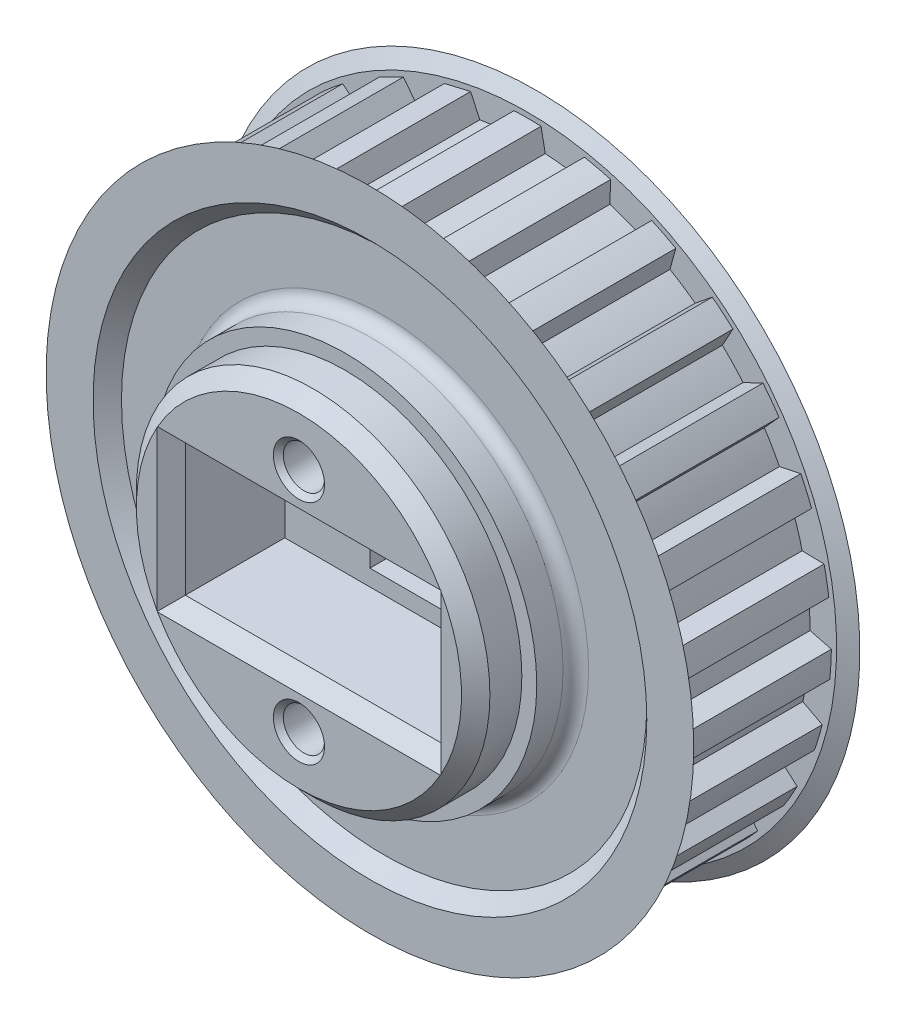
SolidWorks part; units mm, degrees
other "Markup1"
sketch "Sketch8" plane through (-22.8072, 22.8072, -5) normal (-0.0228, 0.8013, -0.5978) x (-0.0343, -0.5983, -0.8006)
material "ABS"
ref_plane "Alzado" through (0, 0, 0) normal (0, 0, 1) x (1, 0, 0)
ref_plane "Planta" through (0, 0, 0) normal (0, 1, 0) x (1, 0, 0)
ref_plane "Vista lateral" through (0, 0, 0) normal (1, 0, 0) x (0, 0, -1)
sketch "Croquis1" plane through (0, 0, 0) normal (0, 0, 1) x (1, 0, 0)
  line L0 (0, 0) -> (0, 14.5885) construction
  line L1 (-0.95, 21.3789) -> (-1.25, 19.8607)
  line L2 (0.95, 21.3789) -> (1.25, 19.8607)
  line L3 (5.8547, 20.5835) -> (5.7965, 19.0371)
  line L4 (4.0059, 21.0217) -> (3.3639, 19.6136)
  line L5 (10.4438, 18.6785) -> (10.0305, 17.1872)
  line L6 (8.7459, 19.5312) -> (7.7964, 18.3092)
  line L7 (14.4698, 15.7665) -> (13.7238, 14.4107)
  line L8 (13.0144, 16.9878) -> (11.8087, 16.0177)
  line L9 (17.7158, 12.0046) -> (16.6772, 10.8573)
  line L10 (16.5812, 13.5286) -> (15.1843, 12.8626)
  line L11 (20.0067, 7.5954) -> (18.7315, 6.7187)
  line L12 (19.2542, 9.3401) -> (17.7413, 9.0142)
  line L13 (21.2191, 2.7768) -> (19.776, 2.2178)
  line L14 (20.8891, 4.648) -> (19.3419, 4.6798)
  line L15 (21.2875, -2.1915) -> (19.7544, -2.4027)
  line L16 (21.398, -0.2947) -> (19.8998, 0.0931)
  line L17 (20.2083, -7.0416) -> (18.6678, -6.8936)
  line L18 (20.7532, -5.2214) -> (19.3848, -4.4986)
  line L19 (18.0397, -11.5122) -> (16.5749, -11.0129)
  line L20 (18.9897, -9.8667) -> (17.8249, -8.8478)
  line L21 (14.8985, -15.3621) -> (13.5883, -14.5385)
  line L22 (16.2024, -13.9801) -> (15.304, -12.72)
  line L23 (10.9542, -18.3838) -> (9.8693, -17.2803)
  line L24 (12.5416, -17.3398) -> (11.958, -15.9065)
  line L25 (6.4193, -20.4145) -> (5.6181, -19.0905)
  line L26 (8.2047, -19.7647) -> (7.9674, -18.2354)
  line L27 (1.5384, -21.3446) -> (1.0641, -19.8715)
  line L28 (3.4255, -21.1241) -> (3.5472, -19.5813)
  line L29 (-3.4255, -21.1241) -> (-3.5472, -19.5813)
  line L30 (-1.5384, -21.3446) -> (-1.0641, -19.8715)
  line L31 (-8.2047, -19.7647) -> (-7.9674, -18.2354)
  line L32 (-6.4193, -20.4145) -> (-5.6181, -19.0905)
  line L33 (-12.5416, -17.3398) -> (-11.958, -15.9065)
  line L34 (-10.9542, -18.3838) -> (-9.8693, -17.2803)
  line L35 (-16.2024, -13.9801) -> (-15.304, -12.72)
  line L36 (-14.8985, -15.3621) -> (-13.5883, -14.5385)
  line L37 (-18.9897, -9.8667) -> (-17.8249, -8.8478)
  line L38 (-18.0397, -11.5122) -> (-16.5749, -11.0129)
  line L39 (-20.7532, -5.2214) -> (-19.3848, -4.4986)
  line L40 (-20.2083, -7.0416) -> (-18.6678, -6.8936)
  line L41 (-21.398, -0.2947) -> (-19.8998, 0.0931)
  line L42 (-21.2875, -2.1915) -> (-19.7544, -2.4027)
  line L43 (-20.8891, 4.648) -> (-19.3419, 4.6798)
  line L44 (-21.2191, 2.7768) -> (-19.776, 2.2178)
  line L45 (-19.2542, 9.3401) -> (-17.7413, 9.0142)
  line L46 (-20.0067, 7.5954) -> (-18.7315, 6.7187)
  line L47 (-16.5812, 13.5286) -> (-15.1843, 12.8626)
  line L48 (-17.7158, 12.0046) -> (-16.6772, 10.8573)
  line L49 (-13.0144, 16.9878) -> (-11.8087, 16.0177)
  line L50 (-14.4698, 15.7665) -> (-13.7238, 14.4107)
  line L51 (-8.7459, 19.5312) -> (-7.7964, 18.3092)
  line L52 (-10.4438, 18.6785) -> (-10.0305, 17.1872)
  line L53 (-10.4438, 18.6785) -> (-8.7459, 19.5312)
  line L54 (-4.0059, 21.0217) -> (-3.3639, 19.6136)
  line L55 (-5.8547, 20.5835) -> (-5.7965, 19.0371)
  line L56 (-5.8547, 20.5835) -> (-4.0059, 21.0217)
  arc A0 (-10.0305, 17.1872) -> (-11.8087, 16.0177) centre (0, 0) ccw
  arc A1 (3.3639, 19.6136) -> (1.25, 19.8607) centre (0, 0) ccw
  arc A2 (-5.7965, 19.0371) -> (-7.7964, 18.3092) centre (0, 0) ccw
  arc A9 (-13.0144, 16.9878) -> (-14.4698, 15.7665) centre (0, 0) ccw
  arc A10 (-16.5812, 13.5286) -> (-17.7158, 12.0046) centre (0, 0) ccw
  arc A11 (5.8547, 20.5835) -> (4.0059, 21.0217) centre (0, 0) ccw
  arc A12 (0.95, 21.3789) -> (-0.95, 21.3789) centre (0, 0) ccw
  arc A16 (10.4438, 18.6785) -> (8.7459, 19.5312) centre (0, 0) ccw
  arc A17 (14.4698, 15.7665) -> (13.0144, 16.9878) centre (0, 0) ccw
  arc A18 (17.7158, 12.0046) -> (16.5812, 13.5286) centre (0, 0) ccw
  arc A19 (20.0067, 7.5954) -> (19.2542, 9.3401) centre (0, 0) ccw
  arc A20 (21.2191, 2.7768) -> (20.8891, 4.648) centre (0, 0) ccw
  arc A21 (21.2875, -2.1915) -> (21.398, -0.2947) centre (0, 0) ccw
  arc A22 (20.2083, -7.0416) -> (20.7532, -5.2214) centre (0, 0) ccw
  arc A23 (18.0397, -11.5122) -> (18.9897, -9.8667) centre (0, 0) ccw
  arc A24 (14.8985, -15.3621) -> (16.2024, -13.9801) centre (0, 0) ccw
  arc A25 (10.9542, -18.3838) -> (12.5416, -17.3398) centre (0, 0) ccw
  arc A26 (-8.2047, -19.7647) -> (-6.4193, -20.4145) centre (0, 0) ccw
  arc A27 (-12.5416, -17.3398) -> (-10.9542, -18.3838) centre (0, 0) ccw
  arc A28 (-16.2024, -13.9801) -> (-14.8985, -15.3621) centre (0, 0) ccw
  arc A29 (-20.7532, -5.2214) -> (-20.2083, -7.0416) centre (0, 0) ccw
  arc A30 (-21.398, -0.2947) -> (-21.2875, -2.1915) centre (0, 0) ccw
  arc A31 (-20.8891, 4.648) -> (-21.2191, 2.7768) centre (0, 0) ccw
  arc A32 (-19.2542, 9.3401) -> (-20.0067, 7.5954) centre (0, 0) ccw
  arc A33 (-3.4255, -21.1241) -> (-1.5384, -21.3446) centre (0, 0) ccw
  arc A34 (1.5384, -21.3446) -> (3.4255, -21.1241) centre (0, 0) ccw
  arc A35 (6.4193, -20.4145) -> (8.2047, -19.7647) centre (0, 0) ccw
  arc A36 (7.7964, 18.3092) -> (5.7965, 19.0371) centre (0, 0) ccw
  arc A37 (11.8087, 16.0177) -> (10.0305, 17.1872) centre (0, 0) ccw
  arc A39 (-1.25, 19.8607) -> (-3.3639, 19.6136) centre (0, 0) ccw
  arc A43 (15.1843, 12.8626) -> (13.7238, 14.4107) centre (0, 0) ccw
  arc A44 (17.7413, 9.0142) -> (16.6772, 10.8573) centre (0, 0) ccw
  arc A45 (19.3419, 4.6798) -> (18.7315, 6.7187) centre (0, 0) ccw
  arc A46 (19.8998, 0.0931) -> (19.776, 2.2178) centre (0, 0) ccw
  arc A47 (19.3848, -4.4986) -> (19.7544, -2.4027) centre (0, 0) ccw
  arc A48 (17.8249, -8.8478) -> (18.6678, -6.8936) centre (0, 0) ccw
  arc A49 (15.304, -12.72) -> (16.5749, -11.0129) centre (0, 0) ccw
  arc A50 (11.958, -15.9065) -> (13.5883, -14.5385) centre (0, 0) ccw
  arc A51 (7.9674, -18.2354) -> (9.8693, -17.2803) centre (0, 0) ccw
  arc A52 (3.5472, -19.5813) -> (5.6181, -19.0905) centre (0, 0) ccw
  arc A53 (-1.0641, -19.8715) -> (1.0641, -19.8715) centre (0, 0) ccw
  arc A54 (-5.6181, -19.0905) -> (-3.5472, -19.5813) centre (0, 0) ccw
  arc A55 (-9.8693, -17.2803) -> (-7.9674, -18.2354) centre (0, 0) ccw
  arc A56 (-13.5883, -14.5385) -> (-11.958, -15.9065) centre (0, 0) ccw
  arc A57 (-16.5749, -11.0129) -> (-15.304, -12.72) centre (0, 0) ccw
  arc A58 (-18.6678, -6.8936) -> (-17.8249, -8.8478) centre (0, 0) ccw
  arc A59 (-19.7544, -2.4027) -> (-19.3848, -4.4986) centre (0, 0) ccw
  arc A60 (-19.776, 2.2178) -> (-19.8998, 0.0931) centre (0, 0) ccw
  arc A61 (-18.7315, 6.7187) -> (-19.3419, 4.6798) centre (0, 0) ccw
  arc A62 (-16.6772, 10.8573) -> (-17.7413, 9.0142) centre (0, 0) ccw
  arc A63 (-13.7238, 14.4107) -> (-15.1843, 12.8626) centre (0, 0) ccw
  arc A71 (-18.9897, -9.8667) -> (-18.0397, -11.5122) centre (0, 0) ccw
  circle A72 centre (0, 0) radius 1.5
  point P151 (0, 0)
  dimension "D1" = 21.4
  dimension "D6" = 3
  dimension "D5" = 1.5
  dimension "D2" = 2.5
  dimension "D3" = 1.9
  dimension "D4" = 27
extrude "Saliente-Extruir1" add sketch "Croquis1" along normal blind 10.5
sketch "Croquis2" plane through (0, 0, 10.5) normal (0, 0, 1) x (1, 0, 0)
  circle A0 centre (0, 0) radius 23.5
  circle A1 centre (0, 0) radius 1.5
  circle A2 centre (0, 0) radius 1.5 construction
  dimension "D1" = 47
extrude "Saliente-Extruir2" add sketch "Croquis2" along normal blind 0.6
sketch "Croquis3" plane through (0, 0, 11.1) normal (0, 0, 1) x (1, 0, 0)
  circle A0 centre (0, 0) radius 1.5
  circle A1 centre (0, 0) radius 12.45
  circle A3 centre (0, 0) radius 1.5 construction
  dimension "D1" = 24.9
sketch "Croquis4" plane through (0, 0, 0) normal (0, 0, -1) x (-1, 0, 0)
  circle A0 centre (0, 0) radius 1.5
  circle A1 centre (0, 0) radius 12.45
  circle A2 centre (0, 0) radius 1.5 construction
  dimension "D1" = 24.9
extrude "Saliente-Extruir4" add sketch "Croquis4" along normal blind 5.25
sketch "Croquis6" plane through (0, 0, 0) normal (0, 0, -1) x (-1, 0, 0)
  circle A0 centre (0, 0) radius 23.5
  circle A1 centre (0, 0) radius 1.5
  circle A2 centre (0, 0) radius 1.5 construction
  dimension "D1" = 47
extrude "Saliente-Extruir6" add sketch "Croquis6" along normal blind 0.6
sketch "Sketch6" plane through (0, 0, -0.6) normal (0, 0, -1) x (-1, 0, 0)
  circle A0 centre (0, 0) radius 12.45
  circle A1 centre (0, 0) radius 18.5
  circle A2 centre (0, 0) radius 12.45 construction
  dimension "D1" = 37
extrude "Cut-Extrude3" cut sketch "Sketch6" against normal blind 1
sketch "Croquis5" plane through (0, 0, 0.4) normal (0, 0, -1) x (-1, 0, 0)
  circle A0 centre (0, 0) radius 1.5
  circle A1 centre (0, 0) radius 13.5
  circle A2 centre (0, 0) radius 1.5 construction
  dimension "D1" = 27
extrude "Saliente-Extruir5" add sketch "Croquis5" along normal blind 2.65
chamfer "Chaflán2" distance 1 angle 60 2 edges at (-23.5, 0, 0) (23.5, 0, 10.5)
extrude "Saliente-Extruir7" add sketch "Croquis3" along normal blind 5
sketch "Sketch7" plane through (0, 0, 11.1) normal (0, 0, 1) x (1, 0, 0)
  circle A0 centre (0, 0) radius 12.45
  circle A1 centre (0, 0) radius 18.5
  circle A2 centre (0, 0) radius 12.45 construction
  dimension "D1" = 37
extrude "Cut-Extrude4" cut sketch "Sketch7" against normal blind 1
chamfer "Chaflán4" distance 1 angle 45 1 edges at (12.45, 0, 16.1)
sketch "Croquis7" plane through (0, 0, 10.1) normal (0, 0, 1) x (1, 0, 0)
  circle A0 centre (0, 0) radius 1.5
  circle A1 centre (0, 0) radius 13.5
  circle A2 centre (0, 0) radius 1.5 construction
  dimension "D1" = 27
extrude "Saliente-Extruir8" add sketch "Croquis7" along normal blind 2.75
sketch "Croquis8" plane through (0, 0, 0) normal (0, 0, 1) x (1, 0, 0)
  line L0 (0, 0) -> (6.706, 0) construction
  line L1 (-3, 3.5) -> (3, 3.5)
  line L2 (-3, 3.5) -> (-3, -3.5)
  line L3 (-3, -3.5) -> (3, -3.5)
  line L4 (3, 3.5) -> (3, -3.5)
  line L5 (-3, 3.5) -> (3, -3.5) construction
  line L6 (-3, -3.5) -> (3, 3.5) construction
  circle A0 centre (0, 8) radius 1.45
  circle A1 centre (0, -8) radius 1.45
  point P0 (0, 0)
  dimension "D1" = 2.9
  dimension "D2" = 7
  dimension "D3" = 6
  dimension "D4" = 16
extrude "Cortar-Extruir1" cut sketch "Croquis8" against normal through all both and the other way through all
sketch "Croquis10" plane through (0, 0, 16.1) normal (0, 0, 1) x (1, 0, 0)
  line L1 (9, 4.65) -> (-9, 4.65)
  line L2 (9, 4.65) -> (9, -4.65)
  line L3 (9, -4.65) -> (-9, -4.65)
  line L4 (-9, 4.65) -> (-9, -4.65)
  line L5 (9, 4.65) -> (-9, -4.65) construction
  line L6 (9, -4.65) -> (-9, 4.65) construction
  point P0 (0, 0)
  dimension "D1" = 9.3
  dimension "D2" = 18
extrude "Cortar-Extruir3" cut sketch "Croquis10" against normal blind 8
chamfer "Chaflán5" distance 1 angle 45 8 edges at (-3, 0, -5.25) (0, 3.5, -5.25) (3, 0, -5.25) (0, -3.5, -5.25) (9, 0, 16.1) (0, 4.65, 16.1) (-9, 0, 16.1) (0, -4.65, 16.1)
sketch "Sketch1" plane through (0, 0, -5.25) normal (0, 0, -1) x (-1, 0, 0)
  circle A0 centre (0, 0) radius 12.45
  circle A1 centre (0, 0) radius 12.45 construction
  circle A2 centre (0, 8) radius 1.45
  circle A3 centre (0, -8) radius 1.45
  circle A4 centre (0, 8) radius 1.45 construction
extrude "Boss-Extrude1" add sketch "Sketch1" against normal blind 5
sketch "Sketch2" plane through (0, 0, -5.25) normal (0, 0, -1) x (-1, 0, 0)
  line L0 (0, 17.274) -> (0, -20.0751) construction
  line L1 (-6.5, 0) -> (6.5, 0) construction
  circle A0 centre (-6.5, 0) radius 1.45
  circle A1 centre (6.5, 0) radius 1.45
  dimension "D1" = 2.9
  dimension "D2" = 13
extrude "Cut-Extrude1" cut sketch "Sketch2" against normal through all
sketch "Sketch4" plane through (0, 0, 16.1) normal (0, 0, 1) x (1, 0, 0)
  line L0 (-3, -3.5) -> (3, -3.5) construction
  line L1 (3, 3.5) -> (-3, 3.5)
  line L2 (3, 3.5) -> (3, -3.5)
  line L3 (3, -3.5) -> (-3, -3.5)
  line L4 (-3, 3.5) -> (-3, -3.5)
  line L5 (3, 3.5) -> (-3, -3.5) construction
  line L6 (3, -3.5) -> (-3, 3.5) construction
  point P0 (0, 0)
  dimension "D1" = 6
extrude "Cut-Extrude2" cut sketch "Sketch4" against normal blind 30
chamfer "Chamfer3" distance 1 angle 45 4 edges at (-3, 0, -5.25) (0, 3.5, -5.25) (3, 0, -5.25) (0, -3.5, -5.25)
chamfer "Chamfer2" distance 0.75 angle 45 1 edges at (-12.45, 0, -5.25)
chamfer "Chamfer4" distance 1 angle 45 2 edges at (18.5, 0, 11.1) (-18.5, 0, -0.6)
chamfer "Chamfer5" distance 0.35 angle 45 8 edges at (1.45, -8, -5.25) (-5.05, 0, -5.25) (5.05, 0, -5.25) (1.45, 8, -5.25) (-7.95, 0, 8.1) (1.45, 8, 16.1) (5.05, 0, 8.1) (1.45, -8, 16.1)
fillet "Fillet1" radius 0.9 2 edges at (-13.5, 0, 0.4) (13.5, 0, 10.1)
